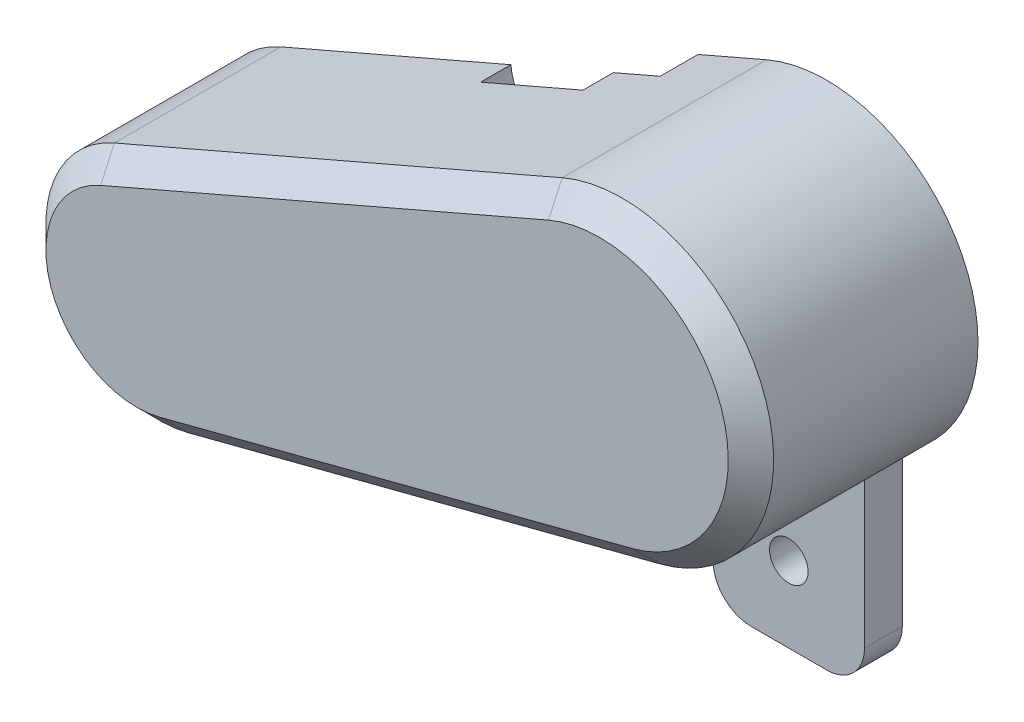
SolidWorks part; units mm, degrees
material "ABS"
ref_plane "Front Plane" through (0, 0, 0) normal (0, 0, 1) x (1, 0, 0)
ref_plane "Top Plane" through (0, 0, 0) normal (0, 1, 0) x (1, 0, 0)
ref_plane "Right Plane" through (0, 0, 0) normal (1, 0, 0) x (0, 0, -1)
sketch "Sketch1" plane through (0, 0, 0) normal (0, 0, 1) x (1, 0, 0)
  circle A0 centre (19, -32.5) radius 12.435 construction
  circle A1 centre (19, -32.5) radius 12.435
  circle A2 centre (-42.15, -53.5167) radius 7.5 construction
  circle A3 centre (-42.15, -53.5167) radius 7.5
ref_plane "Plane1" through (0, 0, 22) normal (0, 0, 1) x (1, 0, 0)
ref_plane "Plane2" through (0, 0, 27) normal (0, 0, 1) x (1, 0, 0)
sketch "Sketch2" plane through (0, 0, 27) normal (0, 0, 1) x (1, 0, 0)
  line L0 (-48.1078, -39.7506) -> (11.0563, -14.1452)
  line L1 (-38.3861, -68.0367) -> (24.0186, -51.8601)
  arc A0 (24.0186, -51.8601) -> (11.0563, -14.1452) centre (19, -32.5) ccw
  arc A1 (-48.1078, -39.7506) -> (-38.3861, -68.0367) centre (-42.15, -53.5167) ccw
  dimension "D1" = 40
  dimension "D2" = 30
extrude "Boss-Extrude1" add sketch "Sketch2" along normal blind 3
sketch "Sketch3" plane through (0, 0, 27) normal (0, 0, -1) x (-1, 0, 0)
  line L0 (46.9162, -42.5038) -> (-12.2479, -16.8984)
  line L1 (-23.2658, -48.9561) -> (39.1389, -65.1327)
  line L2 (48.1078, -39.7506) -> (-11.0563, -14.1452)
  line L3 (-24.0186, -51.8601) -> (38.3861, -68.0367)
  line L4 (48.1078, -39.7506) -> (-11.0563, -14.1452)
  line L5 (-24.0186, -51.8601) -> (38.3861, -68.0367)
  arc A0 (39.1389, -65.1327) -> (46.9162, -42.5038) centre (42.15, -53.5167) ccw
  arc A1 (-12.2479, -16.8984) -> (-23.2658, -48.9561) centre (-19, -32.5) ccw
  arc A2 (38.3861, -68.0367) -> (48.1078, -39.7506) centre (42.15, -53.5167) ccw
  arc A3 (-11.0563, -14.1452) -> (-24.0186, -51.8601) centre (-19, -32.5) ccw
  arc A4 (38.3861, -68.0367) -> (48.1078, -39.7506) centre (42.15, -53.5167) ccw
  arc A5 (-11.0563, -14.1452) -> (-24.0186, -51.8601) centre (-19, -32.5) ccw
  dimension "D1" = 0
  dimension "D2" = 3
extrude "Boss-Extrude2" add sketch "Sketch3" along normal up to surface (27 mm away) up to plane "Front Plane"
chamfer "Chamfer1" distance 3 angle 45 8 edges at (-7.9365, -57.0444, 27) (-53.4984, -57.417, 27) (35.077, -26.9745, 27) (-17.3342, -29.7011, 27) (-7.1838, -59.9484, 30) (37.9141, -25.9994, 30) (-56.3356, -58.3921, 30) (-18.5257, -26.9479, 30)
ref_plane "Plane3" through (0, 0, 5) normal (0, 0, 1) x (1, 0, 0)
sketch "Sketch4" plane through (0, 0, 5) normal (0, 0, 1) x (1, 0, 0)
  line L0 (-20, -37.3667) -> (-20, -69.6667) construction
  line L1 (-20, -37.3667) -> (-20, -69.6667) construction
  line L2 (0, -12.5) -> (0, -52.5) construction
  line L3 (0, -12.5) -> (0, -37.3667) construction
  line L4 (425, -10) -> (0, -10) construction
  line L5 (425, -10) -> (0, -10) construction
  line L6 (425, 10) -> (0, 10) construction
  line L7 (425, 10) -> (0, 10) construction
  line L8 (-20, -37.3667) -> (0, -37.3667) construction
  line L9 (-20, -69.6667) -> (-61.6761, -69.6667) construction
  line L10 (-61.6761, -69.6667) -> (-61.6761, -12.5) construction
  line L11 (-61.6761, -12.5) -> (0, -12.5) construction
  line L12 (-63.6761, -10.5) -> (2, -10.5)
  line L13 (2, -10.5) -> (2, -39.3667)
  line L14 (-18, -39.3667) -> (2, -39.3667)
  line L15 (-18, -39.3667) -> (-18, -71.6667)
  line L16 (-18, -71.6667) -> (-63.6761, -71.6667)
  line L17 (-63.6761, -71.6667) -> (-63.6761, -10.5)
  circle A0 centre (-10, -25.8667) radius 4.75 construction
  circle A1 centre (-10, -25.8667) radius 4.75 construction
  circle A2 centre (-10, -25.8667) radius 7.75
  dimension "D1" = 2
  dimension "D2" = 3
extrude "Cut-Extrude1" cut sketch "Sketch4" against normal up to surface (5 mm away) contours L12 L13 L14 L15 L16 L17 up to face at (-10.9231, -42.7843, 0)
extrude "Cut-Extrude2" cut sketch "Sketch4<3>" along normal blind 4 contours A2
sketch "Sketch4<3>" plane through (0, 0, 5) normal (0, 0, 1) x (1, 0, 0) same geometry as "Sketch4"
sketch "Sketch5" plane through (0, 0, 0) normal (0, 0, -1) x (-1, 0, 0)
  line L0 (-9, -15.0352) -> (-9, 5)
  line L1 (-14, 10) -> (-24, 10)
  line L2 (-29, 5) -> (-29, -15.1795)
  line L3 (-19, 10) -> (-19, -32.5) construction
  line L4 (-11.0563, -14.1452) -> (-2, -18.0647) construction
  line L5 (-11.0563, -14.1452) -> (-9, -15.0352)
  line L6 (-425, 10) -> (0, 10) construction
  arc A0 (-11.0563, -14.1452) -> (-24.0186, -51.8601) centre (-19, -32.5) ccw construction
  arc A1 (-11.0563, -14.1452) -> (-29, -15.1795) centre (-19, -32.5) ccw
  circle A2 centre (-19, 0) radius 2.75
  arc A3 (-24, 10) -> (-29, 5) centre (-24, 5) ccw
  arc A4 (-14, 10) -> (-9, 5) centre (-14, 5) cw
  point P13 (-29, 10)
  point P16 (-9, 10)
  dimension "D2" = 10
  dimension "D3" = 5
  dimension "D4" = 5.5
  dimension "D1" = 20
extrude "Boss-Extrude3" [suppressed] add sketch "Sketch5" against normal blind 5
sketch "Sketch7" plane through (0, 0, 0) normal (0, 0, -1) x (-1, 0, 0)
  line L0 (-9, -55.7533) -> (-9, -70)
  line L1 (-14, -75) -> (-24, -75)
  line L2 (-29, -70) -> (-29, -49.8205)
  line L3 (18, -62.7522) -> (-24.0186, -51.8601) construction
  line L4 (-9, -55.7533) -> (-24.0186, -51.8601)
  line L5 (-19, -32.5) -> (-19, -75) construction
  arc A0 (-11.0563, -14.1452) -> (-24.0186, -51.8601) centre (-19, -32.5) ccw construction
  arc A1 (-29, -49.8205) -> (-24.0186, -51.8601) centre (-19, -32.5) ccw
  arc A2 (-29, -70) -> (-24, -75) centre (-24, -70) ccw
  arc A3 (-14, -75) -> (-9, -70) centre (-14, -70) ccw
  circle A4 centre (-19, -65) radius 2.55
  circle A5 centre (-19, -32.5) radius 12.435 construction
  point P0 (-19, -75)
  point P12 (-29, -75)
  point P15 (-9, -75)
  dimension "D2" = 5
  dimension "D3" = 10
  dimension "D4" = 32.5
  dimension "D5" = 5.1
  dimension "D1" = 20
extrude "Boss-Extrude5" add sketch "Sketch7" against normal blind 5
